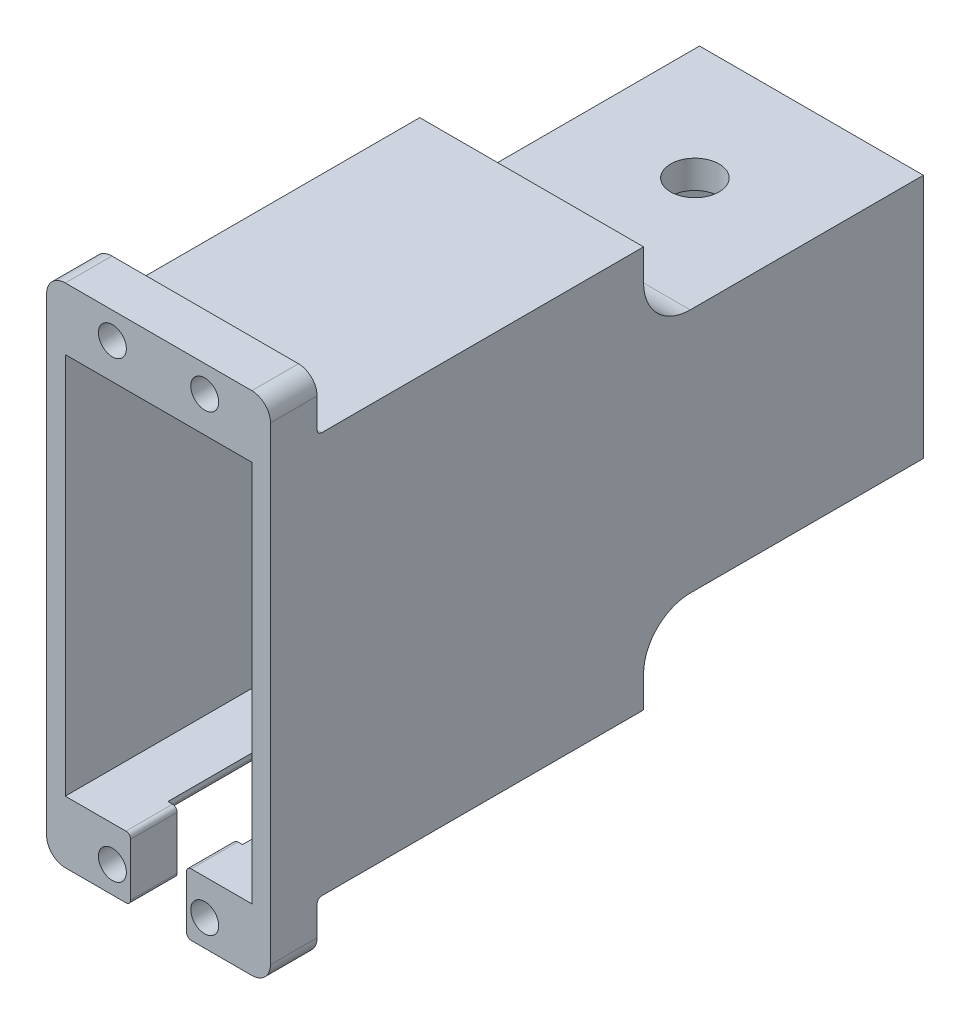
SolidWorks part; units mm, degrees
ref_plane "前视基准面" through (0, 0, 0) normal (0, 0, 1) x (1, 0, 0)
ref_plane "上视基准面" through (0, 0, 0) normal (0, 1, 0) x (1, 0, 0)
ref_plane "右视基准面" through (0, 0, 0) normal (1, 0, 0) x (0, 0, -1)
sketch "草图1" plane through (0, 0, 0) normal (0, 0, 1) x (1, 0, 0)
  line L1 (-12, 12) -> (12, 12)
  line L2 (-12, 12) -> (-12, -12)
  line L3 (-12, -12) -> (12, -12)
  line L4 (12, 12) -> (12, -12)
  line L5 (0, -12) -> (0, 12) construction
  line L6 (-12, 0) -> (12, 0) construction
  point P0 (0, 0)
  dimension "D1" = 24
extrude "凸台-拉伸1" add sketch "草图1" along normal blind 30
sketch "草图2" plane through (0, 0, 0) normal (0, 0, -1) x (-1, 0, 0)
  line L1 (-10.15, 10.15) -> (10.15, 10.15)
  line L2 (-10.15, 10.15) -> (-10.15, -10.15)
  line L3 (-10.15, -10.15) -> (10.15, -10.15)
  line L4 (10.15, 10.15) -> (10.15, -10.15)
  line L5 (0, -10.15) -> (0, 10.15) construction
  line L6 (-10.15, 0) -> (10.15, 0) construction
  point P0 (0, 0)
  dimension "D1" = 20.3
extrude "切除-拉伸1" cut sketch "草图2" against normal through all
sketch "草图3" plane through (0, 0, 30) normal (0, 0, 1) x (1, 0, 0)
  line L0 (-12, -12) -> (12, -12) construction
  line L5 (-12, 12) -> (-7, 12)
  line L6 (-12, 12) -> (-12, -12)
  line L7 (-12, -12) -> (-7, -12)
  line L8 (-7, 12) -> (-7, -12)
  dimension "D1" = 5
extrude "凸台-拉伸3" add sketch "草图3" along normal blind 2
sketch "草图4" plane through (0, 0, 30) normal (0, 0, 1) x (1, 0, 0)
  line L0 (-7, -12) -> (-7, 12) construction
  line L1 (12, -12) -> (-7, -12)
  line L2 (12, -12) -> (12, -7)
  line L3 (12, -7) -> (-7, -7)
  line L4 (-7, -12) -> (-7, -7)
  dimension "D1" = 5
extrude "凸台-拉伸4" add sketch "草图4" along normal blind 2
sketch "草图5" plane through (0, 0, 30) normal (0, 0, 1) x (1, 0, 0)
  line L0 (12, 12) -> (-7, 12) construction
  line L1 (12, -7) -> (7, -7)
  line L2 (12, -7) -> (12, 12)
  line L3 (12, 12) -> (7, 12)
  line L4 (7, -7) -> (7, 12)
  dimension "D1" = 5
extrude "凸台-拉伸5" add sketch "草图5" along normal blind 2
sketch "草图6" plane through (0, 0, 30) normal (0, 0, 1) x (1, 0, 0)
  line L0 (7, 12) -> (7, -7) construction
  line L1 (-7, 12) -> (7, 12)
  line L2 (-7, 12) -> (-7, 7)
  line L3 (-7, 7) -> (7, 7)
  line L4 (7, 12) -> (7, 7)
  dimension "D1" = 5
extrude "凸台-拉伸6" add sketch "草图6" along normal blind 2
sketch "草图7" plane through (0, 0, 32) normal (0, 0, 1) x (1, 0, 0)
  line L0 (12, -12) -> (12, 12) construction
  line L1 (-12, 21.5) -> (12, 21.5)
  line L2 (-12, 21.5) -> (-12, -21.5)
  line L3 (-12, -21.5) -> (12, -21.5)
  line L4 (12, 21.5) -> (12, -21.5)
  line L5 (0, -21.5) -> (0, 21.5) construction
  line L6 (-12, 0) -> (12, 0) construction
  point P0 (0, 0)
  dimension "D2" = 43
extrude "凸台-拉伸7" add sketch "草图7" along normal blind 28
sketch "草图9" plane through (0, 0, 60) normal (0, 0, 1) x (1, 0, 0)
  line L1 (-10, 20.5) -> (10, 20.5)
  line L2 (-10, 20.5) -> (-10, -20.5)
  line L3 (-10, -20.5) -> (10, -20.5)
  line L4 (10, 20.5) -> (10, -20.5)
  line L5 (0, -20.5) -> (0, 20.5) construction
  line L6 (-10, 0) -> (10, 0) construction
  point P0 (0, 0)
  dimension "D1" = 41
  dimension "D2" = 20
extrude "切除-拉伸2" cut sketch "草图9" against normal blind 20
sketch "草图10" plane through (0, 0, 60) normal (0, 0, 1) x (1, 0, 0)
  point P0 (0, 0)
sketch "草图11" plane through (0, 0, 60) normal (0, 0, 1) x (1, 0, 0)
  line L0 (12, -21.5) -> (12, 21.5) construction
  line L1 (-12, 27.15) -> (12, 27.15)
  line L2 (-12, 27.15) -> (-12, -27.15)
  line L3 (-12, -27.15) -> (12, -27.15)
  line L4 (12, 27.15) -> (12, -27.15)
  line L5 (0, -27.15) -> (0, 27.15) construction
  line L6 (-12, 0) -> (12, 0) construction
  point P0 (0, 0)
  dimension "D1" = 54.3
extrude "凸台-拉伸20" add sketch "草图11" along normal blind 10
sketch "草图12" plane through (0, 0, 70) normal (0, 0, 1) x (1, 0, 0)
  line L6 (-10, 20.5) -> (10, 20.5)
  line L7 (-10, 20.5) -> (-10, -20.5)
  line L8 (-10, -20.5) -> (10, -20.5)
  line L9 (10, 20.5) -> (10, -20.5)
  line L10 (0, -20.5) -> (0, 20.5) construction
  line L11 (-10, 0) -> (10, 0) construction
  point P0 (0, 0)
  point P1 (0, 0)
  dimension "D1" = 20
  dimension "D2" = 41
extrude "切除-拉伸4" cut sketch "草图12" against normal blind 10
sketch "草图13" plane through (0, 0, 70) normal (0, 0, 1) x (1, 0, 0)
  line L0 (-23.1116, 0) -> (28.6646, 0) construction
  line L1 (0, 27.7787) -> (0, -31.2712) construction
  circle A0 centre (-4.95, -24.3104) radius 1.5
  circle A1 centre (4.95, -24.3104) radius 1.5
  circle A2 centre (4.95, 24.3104) radius 1.5
  circle A3 centre (-4.95, 24.3104) radius 1.5
  dimension "D1" = 3
  dimension "D2" = 3
  dimension "D3" = 4.95
  dimension "D4" = 4.95
extrude "切除-拉伸5" cut sketch "草图13" against normal blind 10
fillet "圆角2" radius 5 2 edges at (0, -12, 32) (0, 12, 32)
fillet "圆角3" radius 2 4 edges at (12, -27.15, 65) (-12, -27.15, 65) (-12, 27.15, 65) (12, 27.15, 65)
sketch "草图15" plane through (0, 0, 60) normal (0, 0, -1) x (-1, 0, 0)
  line L4 (-12, -21.5) -> (-12, -25.15)
  line L5 (-10, -27.15) -> (10, -27.15)
  line L6 (12, -25.15) -> (12, -21.5)
  line L7 (12, -21.5) -> (-12, -21.5)
  line L8 (-12, -21.5) -> (-12, -25.15)
  line L9 (-10, -27.15) -> (10, -27.15)
  line L10 (12, -25.15) -> (12, -21.5)
  line L11 (12, -21.5) -> (-12, -21.5)
  arc A2 (-12, -25.15) -> (-10, -27.15) centre (-10, -25.15) ccw
  arc A3 (10, -27.15) -> (12, -25.15) centre (10, -25.15) ccw
  arc A4 (-12, -25.15) -> (-10, -27.15) centre (-10, -25.15) ccw
  arc A5 (10, -27.15) -> (12, -25.15) centre (10, -25.15) ccw
  dimension "D1" = 0
extrude "切除-拉伸6" cut sketch "草图15" against normal blind 5
sketch "草图16" plane through (0, 0, 60) normal (0, 0, -1) x (-1, 0, 0)
  line L4 (12, 21.5) -> (12, 25.15)
  line L5 (10, 27.15) -> (-10, 27.15)
  line L6 (-12, 25.15) -> (-12, 21.5)
  line L7 (-12, 21.5) -> (12, 21.5)
  line L8 (12, 21.5) -> (12, 25.15)
  line L9 (10, 27.15) -> (-10, 27.15)
  line L10 (-12, 25.15) -> (-12, 21.5)
  line L11 (-12, 21.5) -> (12, 21.5)
  arc A2 (12, 25.15) -> (10, 27.15) centre (10, 25.15) ccw
  arc A3 (-10, 27.15) -> (-12, 25.15) centre (-10, 25.15) ccw
  arc A4 (12, 25.15) -> (10, 27.15) centre (10, 25.15) ccw
  arc A5 (-10, 27.15) -> (-12, 25.15) centre (-10, 25.15) ccw
  dimension "D1" = 0
extrude "切除-拉伸7" cut sketch "草图16" against normal blind 5
fillet "圆角4" radius 0.5 2 edges at (0, -21.5, 65) (0, 21.5, 65)
sketch "草图17" plane through (0, 0, 40) normal (0, 0, 1) x (1, 0, 0)
  line L1 (-10, 20.5) -> (10, 20.5)
  line L2 (-10, 20.5) -> (-10, -20.5)
  line L3 (-10, -20.5) -> (10, -20.5)
  line L4 (10, 20.5) -> (10, -20.5)
  line L5 (0, -20.5) -> (0, 20.5) construction
  line L6 (-10, 0) -> (10, 0) construction
  point P0 (0, 0)
extrude "凸台-拉伸21" add sketch "草图17" along normal blind 1
sketch "草图18" plane through (0, 0, 70) normal (0, 0, 1) x (1, 0, 0)
  line L0 (-10, -20.5) -> (10, -20.5) construction
  line L2 (-3, -20.5) -> (-3, -29.6944)
  line L3 (-3, -29.6944) -> (3, -29.6944)
  line L4 (3, -20.5) -> (3, -29.6944)
  line L5 (0, -29.6944) -> (0, -20.5) construction
  line L6 (-3, -20.5) -> (3, -20.5) construction
  line L7 (-3, -20.5) -> (3, -20.5)
  point P0 (0, -20.5)
  dimension "D1" = 6
extrude "切除-拉伸8" cut sketch "草图18" against normal up to surface (5 mm away) up to face at (0, -24.9047, 65)
sketch "草图19" plane through (0, 0, 65) normal (0, 0, 1) x (1, 0, 0)
  line L0 (0, -22) -> (0, -20.5) construction
  line L1 (-3, -22) -> (3, -22) construction
  line L2 (-10, -20.5) -> (10, -20.5) construction
  line L4 (-4, -20.5) -> (4, -20.5)
  line L5 (-4, -20.5) -> (-4, -22)
  line L6 (-4, -22) -> (4, -22)
  line L7 (4, -20.5) -> (4, -22)
  line L8 (0, -22) -> (0, -20.5) construction
  line L9 (-4, -21.25) -> (4, -21.25) construction
  point P6 (0, -21.25)
  dimension "D1" = 8
extrude "切除-拉伸9" cut sketch "草图19" against normal up to surface (24 mm away) up to face at (0, 0, 41)
fillet "圆角6" radius 0.5 4 edges at (-3, -20.5, 67.5) (3, -20.5, 67.5) (-3, -27.15, 67.5) (3, -27.15, 67.5)
fillet "圆角7" radius 0.5 1 edges at (0, -21.5, 41)
sketch "草图20" plane through (0, 0, 32) normal (0, 0, -1) x (-1, 0, 0)
  line L1 (-7, 7) -> (7, 7)
  line L2 (-7, 7) -> (-7, -7)
  line L3 (-7, -7) -> (7, -7)
  line L4 (7, 7) -> (7, -7)
  line L5 (0, -7) -> (0, 7) construction
  line L6 (-7, 0) -> (7, 0) construction
  point P0 (0, 0)
extrude "凸台-拉伸22" add sketch "草图20" along normal up to surface (2 mm away) up to face at (0, 0, 30)
fillet "圆角8" radius 0.5 4 edges at (-4, -21.6464, 64.8536) (4, -21.6464, 64.8536) (-4, -21.5, 52.5) (4, -21.5, 52.5)
sketch "草图22" plane through (-12, 0, 0) normal (-1, 0, 0) x (0, 0, 1)
  line L0 (0, 12) -> (27, 12)
  line L1 (32, 21.5) -> (32, 17)
  line L2 (32, 21.5) -> (0, 21.5)
  line L3 (0, 21.5) -> (0, 12)
  line L4 (0, -12) -> (27, -12)
  line L5 (32, -17) -> (32, -21.5)
  line L6 (32, -21.5) -> (0, -21.5)
  line L7 (0, -21.5) -> (0, -12)
  arc A0 (27, 12) -> (32, 17) centre (27, 17) ccw
  arc A1 (27, 12) -> (32, 17) centre (27, 17) ccw construction
  arc A2 (27, -12) -> (32, -17) centre (27, -17) cw
  arc A3 (32, -17) -> (27, -12) centre (27, -17) ccw construction
  line M4 (32, 21.5) -> (32, 17)
  arc M5 (32, 17) -> (27, 12) centre (27, 17) cw
  line M6 (27, 12) -> (0, 12)
  line M8 (0, -12) -> (27, -12)
  arc M9 (27, -12) -> (32, -17) centre (27, -17) cw
  line M10 (32, -17) -> (32, -21.5)
extrude "凸台-拉伸24" add sketch "草图22" against normal blind 24 contours L2 L3 M6 M5 M4 | L7 L6 M10 M9 M8 region at (-12, 16.8153, 15.7326) region at (-12, -16.8153, 15.7326)
sketch "草图23" plane through (0, 0, 0) normal (0, 0, -1) x (-1, 0, 0)
  line L0 (0, 0) -> (0, -10.15)
  line L2 (-10.15, -10.15) -> (10.15, -10.15) construction
  line L3 (0, 13.15) -> (12, 13.15)
  line L4 (12, 21.5) -> (12, -21.5) construction
  line L5 (0, -10.15) -> (0, -13.15)
  line L6 (0, 13.15) -> (-12, 13.15)
  line L7 (-12, -21.5) -> (-12, 21.5) construction
  line L8 (0, -13.15) -> (12, -13.15)
  line L9 (0, -13.15) -> (-12, -13.15)
  line L11 (-12, 13.15) -> (12, 13.15)
  line L12 (-12, 13.15) -> (-12, 21.5)
  line L13 (-12, 21.5) -> (12, 21.5)
  line L14 (12, 13.15) -> (12, 21.5)
  line L15 (-12, -13.15) -> (12, -13.15)
  line L16 (-12, -13.15) -> (-12, -21.5)
  line L17 (-12, -21.5) -> (12, -21.5)
  line L18 (12, -13.15) -> (12, -21.5)
  line M11 (-12, 21.5) -> (-12, -21.5)
  line M12 (-12, -21.5) -> (12, -21.5)
  line M13 (12, -21.5) -> (12, 21.5)
  line M14 (12, 21.5) -> (-12, 21.5)
extrude "切除-拉伸11" cut sketch "草图23" against normal blind 30 contours L6 L3 M13 M14 M11 | L8 L9 M11 M12 M13 region at (0, 17.325, 0) region at (0, -17.325, 0)
sketch "草图25" plane through (12, 0, 0) normal (1, 0, 0) x (0, 0, -1)
  line L0 (-30, 13.15) -> (-25, 13.15)
  line L1 (-30, 13.15) -> (0, 13.15) construction
  line L3 (-30, 21.5) -> (-30, 13.15) construction
  line L4 (-30, 18.15) -> (-30, 13.15)
  line L5 (-30, -13.15) -> (-25, -13.15)
  line L6 (-30, -13.15) -> (-30, -18.15)
  arc A0 (-30, 18.15) -> (-25, 13.15) centre (-25, 18.15) ccw
  arc A1 (-30, -18.15) -> (-25, -13.15) centre (-25, -18.15) cw
  line M8 (0, 13.15) -> (-30, 13.15)
  line M9 (-30, 13.15) -> (-30, 21.5)
extrude "凸台-拉伸25" add sketch "草图25" against normal blind 24 contours A0 M9 M8 | L6 L5 A1 region at (12, 14.2668, 28.8832)
sketch "草图26" plane through (0, -13.15, 0) normal (0, -1, 0) x (-1, 0, 0)
  line L0 (12, -25) -> (-12, 0)
  circle A0 centre (0, -12.5) radius 2.6
extrude "切除-拉伸12" cut sketch "草图26" against normal blind 30 contours L0 A0 | L0 A0 region at (0.796, -13.15, 13.2642) region at (-0.796, -13.15, 11.7358)
